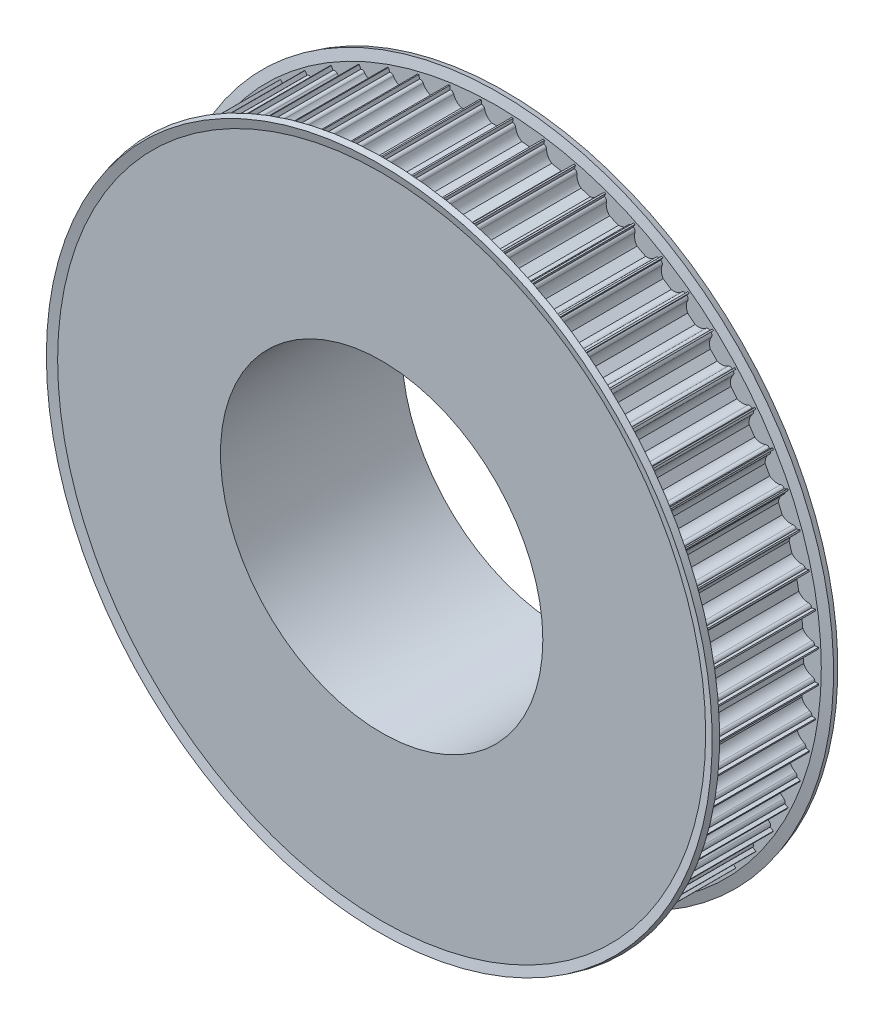
SolidWorks part; units mm, degrees
ref_plane "Front Plane" through (0, 0, 0) normal (0, 0, 1) x (1, 0, 0)
ref_plane "Top Plane" through (0, 0, 0) normal (0, 1, 0) x (1, 0, 0)
ref_plane "Right Plane" through (0, 0, 0) normal (1, 0, 0) x (0, 0, -1)
sketch "Sketch1" plane through (0, 0, 0) normal (1, 0, 0) x (0, 0, -1)
  line L0 (0, 0) -> (45.3408, 0) construction
  line L1 (0, 40) -> (45, 40)
  line L2 (45, 40) -> (45, 55.5)
  line L3 (45, 55.5) -> (30, 55.5)
  line L4 (30, 55.5) -> (30, 80)
  line L5 (30, 80) -> (0, 80)
  line L6 (0, 80) -> (0, 40)
  point P5 (45.3408, 0)
  point P10 (0, 0)
  dimension "D1" = 40
  dimension "D2" = 80
  dimension "D3" = 30
  dimension "D4" = 15
  dimension "D5" = 15.5
revolve "Revolve1" add sketch "Sketch1" angle 360 about L0
sketch "Sketch2" plane through (0, 0, 0) normal (0, 0, 1) x (1, 0, 0)
  line L0 (-3.6742, 79) -> (-3.75, 79)
  line L1 (-3.75, 79) -> (-3.75, 81)
  line L2 (-3.75, 81) -> (3.75, 81)
  line L3 (3.75, 81) -> (3.75, 79)
  line L4 (3.75, 79) -> (3.6742, 79)
  line L5 (-1.199, 76.25) -> (1.199, 76.25)
  arc A0 (2.9394, 78.4) -> (1.199, 76.25) centre (0, 79) cw
  arc A1 (2.9394, 78.4) -> (3.6742, 79) centre (3.6742, 78.25) cw
  arc A2 (-2.9394, 78.4) -> (-3.6742, 79) centre (-3.6742, 78.25) ccw
  arc A3 (-1.199, 76.25) -> (-2.9394, 78.4) centre (0, 79) cw
  point P3 (0, 0)
  point P9 (0, 81)
  point P12 (3, 79)
  point P15 (-3, 79)
  dimension "D1" = 3
  dimension "D5" = 0.75
  dimension "D2" = 79
  dimension "D3" = 7.5
  dimension "D4" = 2
  dimension "D6" = 2.75
extrude "Cut-Extrude1" cut sketch "Sketch2" against normal up to next
pattern_circular "CirPattern1" count 64 over 360 about axis through (0, 0, 0) along (0, 0, 1) of "Cut-Extrude1"
sketch "Sketch3" plane through (0, 0, 0) normal (1, 0, 0) x (0, 0, -1)
  line L0 (15, -40.9775) -> (15, -10.6098) construction
  line L1 (30, -40.9775) -> (0, -40.9775) construction
  line L2 (30, -10.6098) -> (0, -10.6098) construction
  line L3 (30, 55.5) -> (30, 80.4125)
  line L4 (30, 80.4125) -> (30.592, 82.6218)
  line L5 (30.592, 82.6218) -> (29.1431, 83.01)
  line L6 (29.1431, 83.01) -> (28.5, 80.61)
  line L7 (28.5, 80.61) -> (28.5, 55.5)
  line L8 (28.5, 55.5) -> (30, 55.5)
  line L9 (1.5, 55.5) -> (0, 55.5)
  line L10 (1.5, 80.61) -> (1.5, 55.5)
  line L11 (0.8569, 83.01) -> (1.5, 80.61)
  line L12 (-0.592, 82.6218) -> (0.8569, 83.01)
  line L13 (0, 80.4125) -> (-0.592, 82.6218)
  line L14 (0, 55.5) -> (0, 80.4125)
  dimension "D1" = 15
  dimension "D2" = 25.11
  dimension "D3" = 1.5
  dimension "D4" = 2.4
ref_axis "Axis1" through (0, 0, -28.9943) along (0, 0, 1)
revolve "Revolve2" add sketch "Sketch3" angle 360 about axis through (0, 0, -28.9943) along (0, 0, 1)
